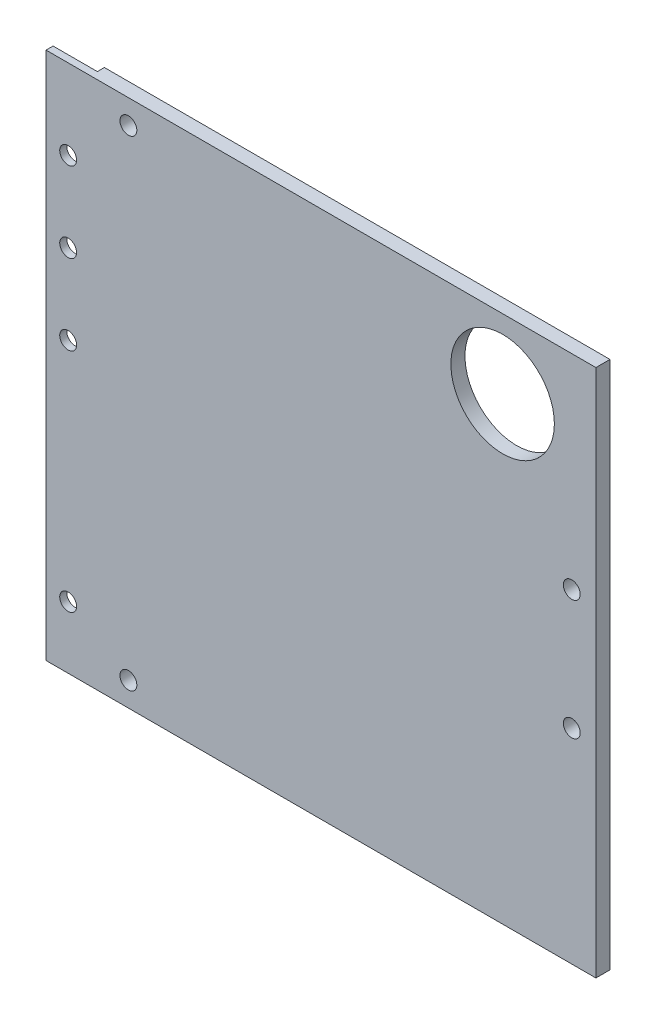
SolidWorks part; units mm, degrees
ref_plane "Front Plane" through (0, 0, 0) normal (0, 0, 1) x (1, 0, 0)
ref_plane "Top Plane" through (0, 0, 0) normal (0, 1, 0) x (1, 0, 0)
ref_plane "Right Plane" through (0, 0, 0) normal (1, 0, 0) x (0, 0, -1)
sketch "Sketch2" plane through (0, -1.0615, 0) normal (0, 0, 1) x (1, 0, 0)
  line L1 (-61.3763, 33.8617) -> (62.7937, 33.8617)
  line L2 (-61.3763, 33.8617) -> (-61.3763, -85.5183)
  line L3 (-61.3763, -85.5183) -> (62.7937, -85.5183)
  line L4 (62.7937, 33.8617) -> (62.7937, -85.5183)
  dimension "D1" = 124.17
  dimension "D2" = 119.38
extrude "Boss-Extrude1" add sketch "Sketch2" along normal blind 3.18
sketch "Sketch3" plane through (0, 0, 0) normal (0, 0, 1) x (1, 0, 0)
  line L0 (-61.3763, 32.8002) -> (-61.3763, -86.5798) construction
  line L8 (62.7937, 32.8002) -> (-61.3763, 32.8002) construction
  line L9 (62.7937, -86.5798) -> (62.7937, 32.8002) construction
  line L10 (-61.3763, -86.5798) -> (62.7937, -86.5798) construction
  circle A2 centre (-42.7763, 27.3482) radius 1.905
  circle A3 centre (41.7297, 17.0902) radius 11.685
  circle A4 centre (-42.7763, -81.1278) radius 1.905
  circle A5 centre (57.3437, -13.3398) radius 1.905
  circle A6 centre (57.3437, -40.4398) radius 1.905
  dimension "D5" = 5.452
  dimension "D1" = 15.71
  dimension "D3" = 23.37
  dimension "D2" = 21.064
  dimension "D4" = 5.452
  dimension "D9" = 27.1
  dimension "D10" = 46.14
  dimension "D11" = 18.6
  dimension "D17" = 18.6
extrude "Cut-Extrude1" cut sketch "Sketch3" along normal blind 23.18
sketch "Sketch5" plane through (-61.3763, 0, 0) normal (-1, 0, 0) x (0, 0, 1)
  line L1 (0, 32.8002) -> (1.59, 32.8002)
  line L2 (0, 32.8002) -> (0, -87.1998)
  line L3 (0, -87.1998) -> (1.59, -87.1998)
  line L4 (1.59, 32.8002) -> (1.59, -87.1998)
  dimension "D1" = 1.59
  dimension "D2" = 120
extrude "Cut-Extrude2" cut sketch "Sketch5" against normal blind 10
sketch "Sketch6" plane through (0, 0, 1.59) normal (0, 0, -1) x (-1, 0, 0)
  line L0 (61.3763, -86.5798) -> (61.3763, 32.8002) construction
  line L1 (51.3763, 32.8002) -> (61.3763, 32.8002) construction
  line L2 (61.3763, -86.5798) -> (51.3763, -86.5798) construction
  circle A0 centre (56.3763, 14.7202) radius 1.905
  circle A1 centre (56.3763, -21.4498) radius 1.905
  circle A2 centre (56.3763, -72.5798) radius 1.905
  circle A6 centre (56.3763, -3.3698) radius 1.905
  dimension "D1" = 5
  dimension "D2" = 5
  dimension "D3" = 5
  dimension "D4" = 5
  dimension "D5" = 36.17
  dimension "D6" = 18.08
  dimension "D7" = 18.08
  dimension "D8" = 14
extrude "Cut-Extrude3" cut sketch "Sketch6" against normal blind 5
